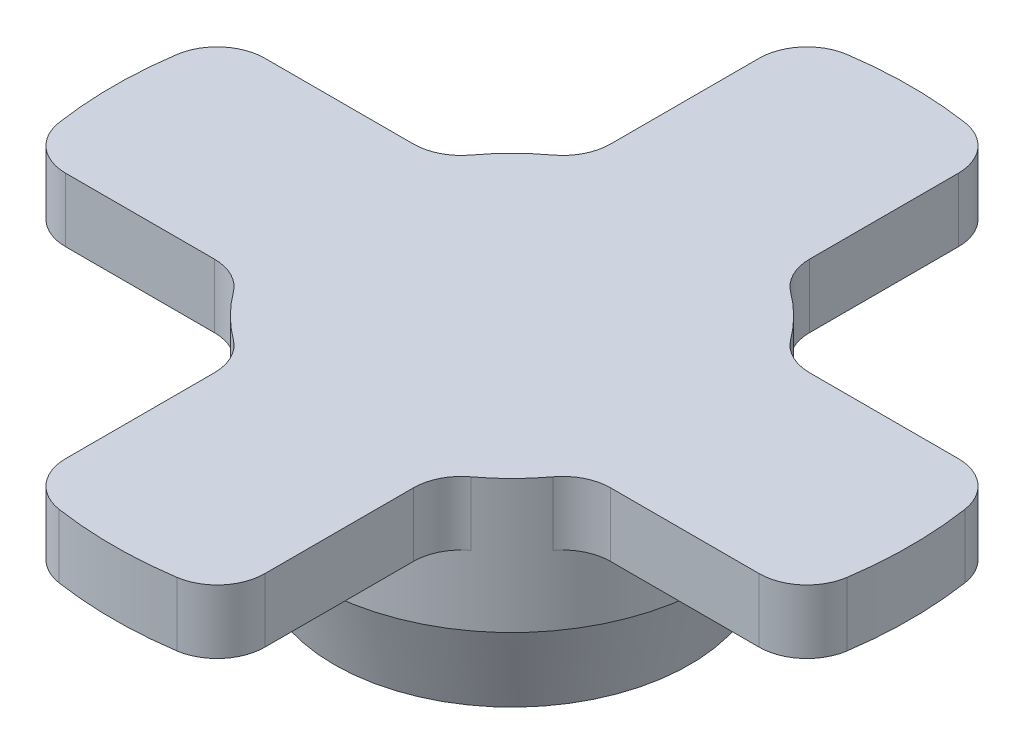
SolidWorks part; units mm, degrees
note: The reader was unsure of these and kept them because the rebuilt part matched: shared geometry of "Sketch1<3>".
ref_plane "Front Plane" through (0, 0, 0) normal (0, 0, 1) x (1, 0, 0)
ref_plane "Top Plane" through (0, 0, 0) normal (0, 1, 0) x (1, 0, 0)
ref_plane "Right Plane" through (0, 0, 0) normal (1, 0, 0) x (0, 0, -1)
sketch "Sketch1" plane through (0, 0, 0) normal (0, 1, 0) x (1, 0, 0)
  line L0 (-3.175, 12.2967) -> (-3.175, 5.4993)
  line L1 (3.175, 12.2967) -> (3.175, 5.4993)
  line L2 (0, 0) -> (0, 12.7) construction
  line L3 (12.2967, 3.175) -> (5.4993, 3.175)
  line L4 (12.2967, -3.175) -> (5.4993, -3.175)
  line L5 (3.175, -12.2967) -> (3.175, -5.4993)
  line L6 (-3.175, -12.2967) -> (-3.175, -5.4993)
  line L7 (-12.2967, -3.175) -> (-5.4993, -3.175)
  line L8 (-12.2967, 3.175) -> (-5.4993, 3.175)
  circle A0 centre (0, 0) radius 6.35
  circle A1 centre (0, 0) radius 3.4925
  circle A2 centre (0, 0) radius 12.7
  point P25 (0, 0)
  dimension "D1" = 12.7
  dimension "D2" = 6.985
  dimension "D3" = 25.4
  dimension "D4" = 6.35
  dimension "D5" = 3.175
  dimension "D6" = 4
extrude "Boss-Extrude1" add sketch "Sketch1" along normal blind 2.032
extrude "Boss-Extrude2" add sketch "Sketch1<3>" against normal blind 4.7625
sketch "Sketch1<3>" plane through (0, 0, 0) normal (0, 1, 0) x (1, 0, 0) same geometry as "Sketch1"
chamfer "Chamfer1" distance 2.54 angle 15 2 edges at (0, -4.7625, 6.35) (0, -4.7625, 3.4925)
fillet "Fillet2" radius 1.524 16 edges at (-3.175, 1.016, -12.2967) (3.175, 1.016, -12.2967) (3.175, 1.016, -5.4993) (12.2967, 1.016, -3.175) (12.2967, 1.016, 3.175) (5.4993, 1.016, 3.175) (5.4993, 1.016, -3.175) (3.175, 1.016, 5.4993) (3.175, 1.016, 12.2967) (-3.175, 1.016, 12.2967) (-3.175, 1.016, 5.4993) (-5.4993, 1.016, 3.175) (-12.2967, 1.016, 3.175) (-12.2967, 1.016, -3.175) (-5.4993, 1.016, -3.175) (-3.175, 1.016, -5.4993)
